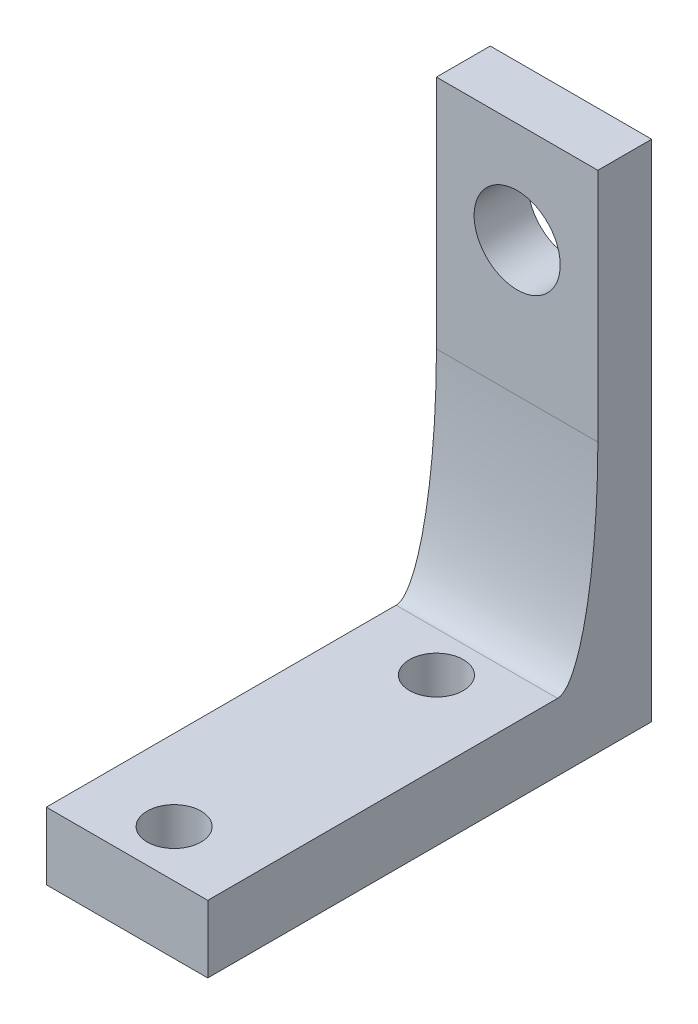
SolidWorks part; units mm, degrees
ref_plane "Front Plane" through (0, 0, 0) normal (0, 0, 1) x (1, 0, 0)
ref_plane "Top Plane" through (0, 0, 0) normal (0, 1, 0) x (1, 0, 0)
ref_plane "Right Plane" through (0, 0, 0) normal (1, 0, 0) x (0, 0, -1)
sketch "Sketch1" plane through (0, 0, 0) normal (0, 0, 1) x (1, 0, 0)
  line L1 (0, 0) -> (12, 0)
  line L2 (0, 0) -> (0, 32.5)
  line L3 (0, 32.5) -> (12, 32.5)
  line L4 (12, 0) -> (12, 32.5)
  circle A0 centre (6, 25) radius 3.2
  dimension "D3" = 7.5
  dimension "D4" = 6
  dimension "D1" = 12
  dimension "D2" = 32.5
extrude "Boss-Extrude1" add sketch "Sketch1" along normal blind 4
sketch "Sketch2" plane through (0, 0, 0) normal (0, -1, 0) x (1, 0, 0)
  line L1 (0, 0) -> (12, 0)
  line L2 (0, 0) -> (0, 33)
  line L3 (0, 33) -> (12, 33)
  line L4 (12, 0) -> (12, 33)
  circle A0 centre (6, 10) radius 2
  circle A1 centre (6, 29.5) radius 2
  dimension "D3" = 3.5
  dimension "D4" = 23
  dimension "D5" = 6
  dimension "D6" = 6
  dimension "D7" = 4
  dimension "D8" = 4
  dimension "D1" = 12
  dimension "D2" = 33
extrude "Boss-Extrude2" add sketch "Sketch2" along normal blind 5
fillet "Fillet1" radius 3 1 edges at (6, 0, 4) second distance 15 first distance on face at (6, 0, 27.5)
